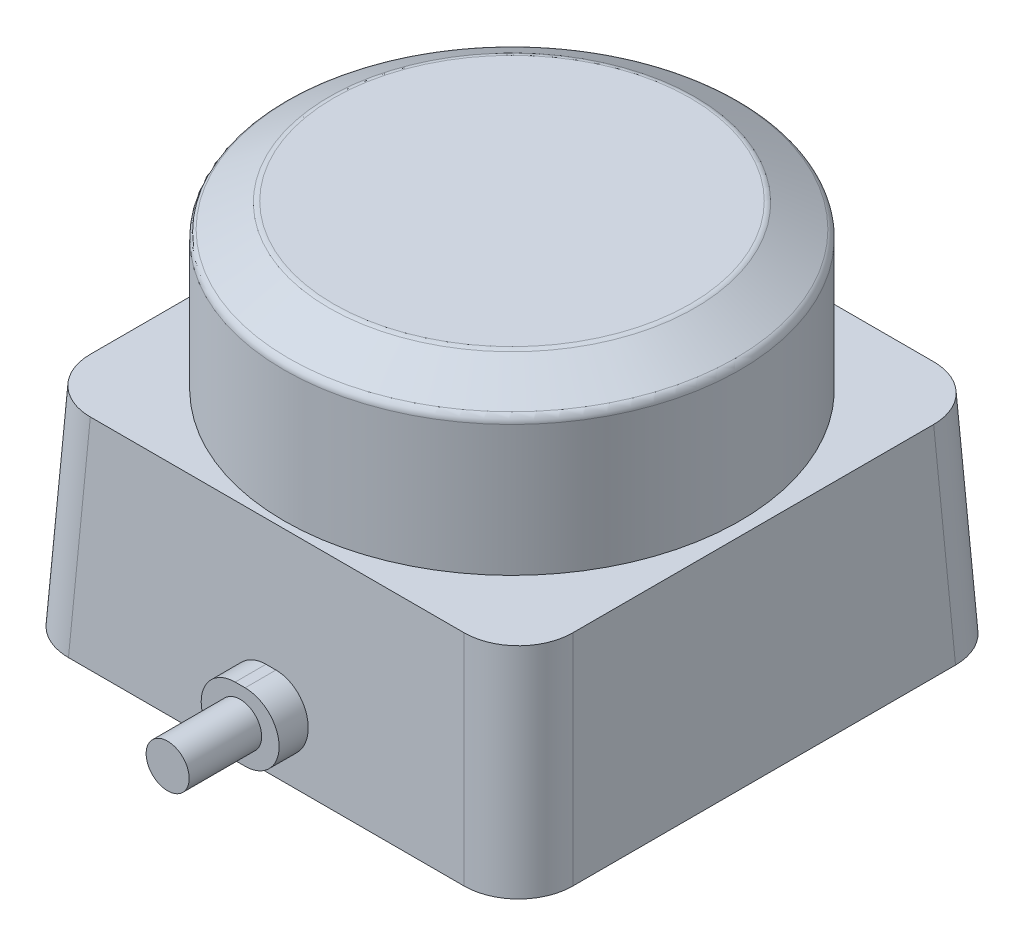
SolidWorks part; units mm, degrees
ref_plane "Front Plane" through (0, 0, 0) normal (0, 0, 1) x (1, 0, 0)
ref_plane "Top Plane" through (0, 0, 0) normal (0, 1, 0) x (1, 0, 0)
ref_plane "Right Plane" through (0, 0, 0) normal (1, 0, 0) x (0, 0, -1)
sketch "Sketch1" plane through (0, 0, 0) normal (0, 1, 0) x (1, 0, 0)
  line L1 (27.825, -27.1103) -> (-27.825, -27.1103)
  line L2 (27.825, -27.1103) -> (27.825, 27.1103)
  line L3 (27.825, 27.1103) -> (-27.825, 27.1103)
  line L4 (-27.825, -27.1103) -> (-27.825, 27.1103)
  line L5 (27.825, -27.1103) -> (-27.825, 27.1103) construction
  line L6 (27.825, 27.1103) -> (-27.825, -27.1103) construction
  point P0 (0, 0)
  dimension "D1" = 55.65
extrude "Boss-Extrude1" add sketch "Sketch1" along normal blind 23 draft 3
sketch "Sketch2" plane through (0, 23, 0) normal (0, 1, 0) x (1, 0, 0)
  circle A0 centre (0, 0) radius 25.15
  dimension "D1" = 50.3
extrude "Boss-Extrude2" add sketch "Sketch2" along normal blind 18
chamfer "Chamfer1" distance 3 angle 60 1 edges at (0, 41, 25.15) first distance on face at (0, 41, 25.15)
sketch "Sketch3" plane through (0, 0, 0) normal (0, 0, 1) x (1, 0, 0)
  line L0 (0.55, 6) -> (-0.55, 6) construction
  line L1 (0.55, 2.25) -> (-0.55, 2.25)
  line L2 (0.55, 9.75) -> (-0.55, 9.75)
  line L3 (-27.825, 0) -> (27.825, 0) construction
  arc A0 (0.55, 2.25) -> (0.55, 9.75) centre (0.55, 6) ccw
  arc A1 (-0.55, 9.75) -> (-0.55, 2.25) centre (-0.55, 6) ccw
  point P2 (0, 6)
  dimension "D1" = 7.5
  dimension "D2" = 1.1
  dimension "D3" = 6
extrude "Boss-Extrude3" add sketch "Sketch3" along normal blind 30
sketch "Sketch4" plane through (0, 0, 30) normal (0, 0, 1) x (1, 0, 0)
  circle A0 centre (0, 6) radius 2.375
  dimension "D1" = 4.75
extrude "Boss-Extrude4" add sketch "Sketch4" along normal blind 8
sketch "Sketch5" plane through (0, 0, 0) normal (0, -1, 0) x (1, 0, 0)
  line L1 (21.4, -21.4) -> (-21.4, -21.4) construction
  line L2 (21.4, -21.4) -> (21.4, 21.4) construction
  line L3 (21.4, 21.4) -> (-21.4, 21.4) construction
  line L4 (-21.4, -21.4) -> (-21.4, 21.4) construction
  line L5 (21.4, -21.4) -> (-21.4, 21.4) construction
  line L6 (21.4, 21.4) -> (-21.4, -21.4) construction
  circle A0 centre (-21.4, 21.4) radius 1.25
  circle A1 centre (21.4, 21.4) radius 1.25
  circle A2 centre (21.4, -21.4) radius 1.25
  circle A3 centre (-21.4, -21.4) radius 1.25
  point P0 (0, 0)
  dimension "D1" = 2.5
  dimension "D2" = 42.8
extrude "Cut-Extrude1" cut sketch "Sketch5" against normal blind 5
chamfer "Chamfer2" distance 0.2 angle 60 4 edges at (-21.4, 0, 20.15) (21.4, 0, -22.65) (-21.4, 0, -22.65) (21.4, 0, 20.15) first distance on face at (-21.4, 0, -22.65)
fillet "Fillet1" radius 6 4 edges at (-27.2223, 11.5, 26.5076) (-27.2223, 11.5, -26.5076) (27.2223, 11.5, -26.5076) (27.2223, 11.5, 26.5076)
fillet "Fillet2" radius 1 2 edges at (0, 41, 19.9538) (0, 38, 25.15)
